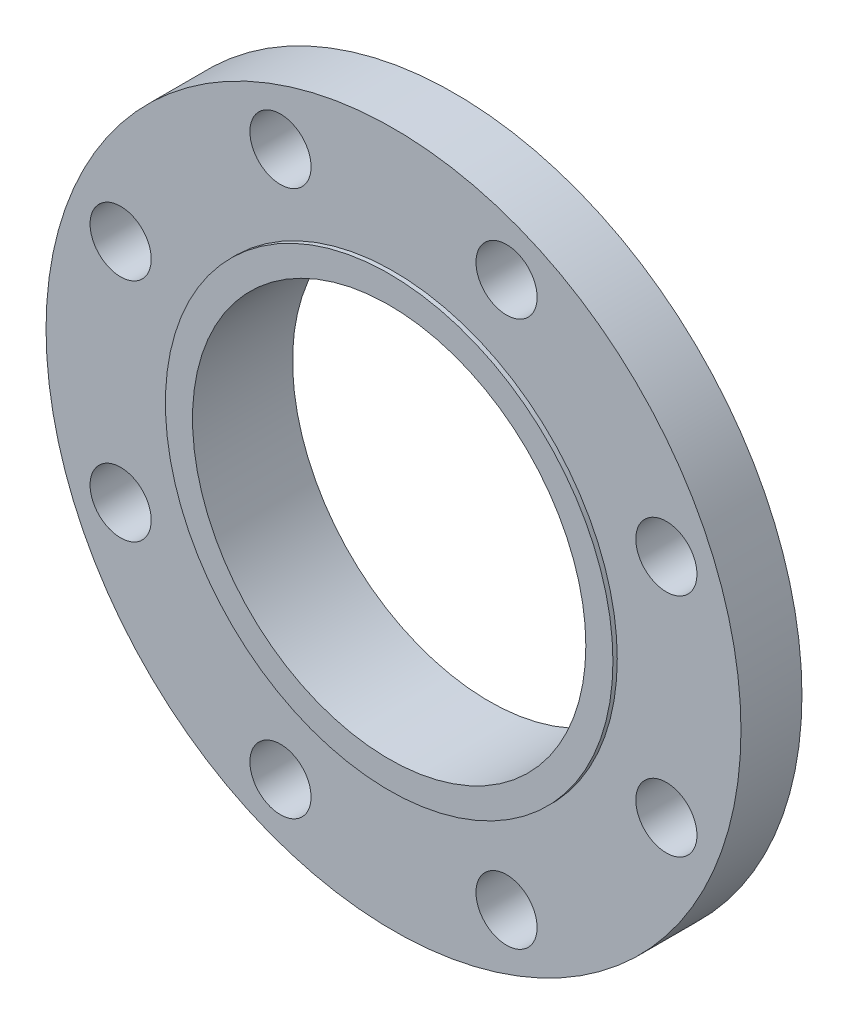
SolidWorks part; units mm, degrees
ref_plane "front" through (0, 0, 0) normal (0, 0, 1) x (1, 0, 0)
ref_plane "top" through (0, 0, 0) normal (0, 1, 0) x (1, 0, 0)
ref_plane "side" through (0, 0, 0) normal (1, 0, 0) x (0, 0, -1)
other "Configuration Table"
sketch "Hub Diameter" plane through (0, 0, 0) normal (0, 0, 1) x (1, 0, 0)
  circle A0 centre (0, 0) radius 81.788
  dimension "Diameter of Hub X" = 163.576
extrude "Hub" add sketch "Hub Diameter" against normal blind 36.576
ref_plane "Flange starting plane" through (0, 0, -1.5875) normal (0, 0, 1) x (1, 0, 0)
ref_plane "Flange end plane" through (0, 0, -23.876) normal (0, 0, 1) x (1, 0, 0)
sketch "Flange Diameter" plane through (0, 0, -1.5875) normal (0, 0, 1) x (1, 0, 0)
  circle A0 centre (0, 0) radius 127
  dimension "Outside Diameter of Flange O" = 254
extrude "Flange" add sketch "Flange Diameter" against normal up to surface (22.2885 mm away) up to plane "Flange end plane"
ref_axis "Axis of Revolution for Bore" through (0, 0, -50) along (0, 0, 1)
sketch "Bolt Diameter" plane through (0, 0, -1.5875) normal (0, 0, 1) x (1, 0, 0)
  line L0 (0, 19.05) -> (0, -19.05) construction
  line L1 (9.3218, 22.5047) -> (-9.3218, -22.5047) construction
  circle A0 centre (41.3107, 99.7328) radius 11.176
  circle A1 centre (0, 0) radius 107.95 construction
  point P0 (0, 0)
  dimension "Diameter of Bolt Holes" = 22.352
  dimension "Diameter of Bolt Circle" = 215.9
  dimension "Angle" = 22.5
sketch "Revolution profile for Bore" plane through (0, 0, 0) normal (0, 1, 0) x (1, 0, 0)
  line L0 (0, -19.5213) -> (0, 228.6) construction
  line L1 (0, 1.5875) -> (0, 0) construction
  line L2 (0, 0) -> (71.882, 0)
  line L3 (71.882, 0) -> (71.882, 228.6)
  line L4 (71.882, 228.6) -> (0, 228.6)
  line L5 (0, 228.6) -> (0, 0)
  point P4 (0, 0)
  dimension "D2" = 143.764
  dimension "Hub Length Y" = 228.6
revolve "Bore" cut sketch "Revolution profile for Bore" angle 360 about L0
extrude "Bolt Hole" cut sketch "Bolt Diameter" against normal through all
pattern_circular "Bolt Hole Pattern" count 8 every 45 about axis through (0, 0, -50) along (0, 0, 1) of "Bolt Hole"
sketch "Sketch1" plane through (0, 0, 0) normal (0, 1, 0) x (1, 0, 0)
  line L1 (0, -19.5213) -> (0, 228.6) construction
  line L2 (-71.882, 0) -> (71.882, 0) construction
  point P0 (0, 6.35)
  point P6 (0, 0)
  dimension "D1" = 6.35
other "CPoint1" parameters "Diameter"=127, "StubLength"=0
ref_axis "Axis1" through (0, 0, -16.35) along (0, 0, 1)
other "RPoint1"
ref_axis "Axis of Rotation" through (0, 0, -36.576) along (0, 0, 1)
ref_axis "Vertical" through (0, 0, -6.35) along (0, 1, 0)
equation "\"flange height@Flange starting plane\" =  ( \"Hub Length Y@Hub\" - \"Thickness of Flange C@Flange end plane\" )  / 3"
equation "\"angular position of Bolt Holes@Bolt Hole Pattern\" = 360/\"Number of Bolt Holes@Bolt Hole Pattern\""
